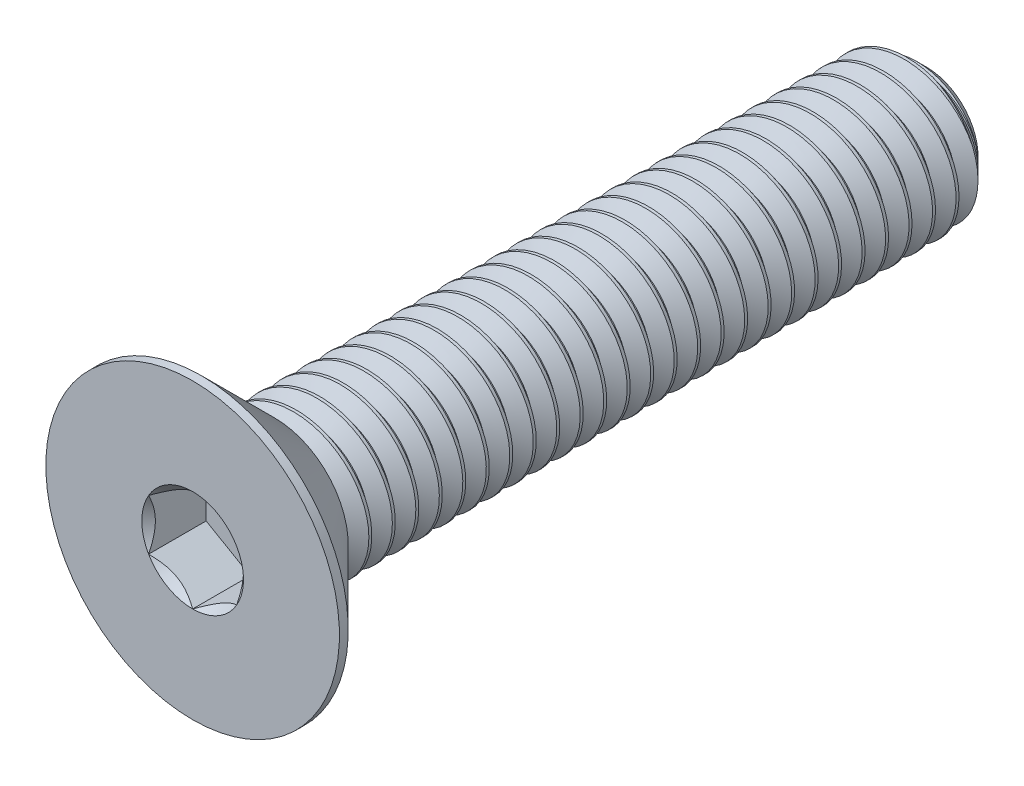
SolidWorks part; units mm, degrees
ref_plane "Front" through (0, 0, 0) normal (0, 0, 1) x (1, 0, 0)
ref_plane "Top" through (0, 0, 0) normal (0, 1, 0) x (1, 0, 0)
ref_plane "Right" through (0, 0, 0) normal (1, 0, 0) x (0, 0, -1)
sketch "Sketch1" plane through (0, 0, 0) normal (1, 0, 0) x (0, 0, -1)
  line L0 (-12.5, 5) -> (-12.2, 5) construction
  line L1 (-12.2, 5) -> (-9.7, 2.5) construction
  line L2 (-12.5, 2.5) -> (12.5, 2.5) construction
  line L3 (12.5, 2.5) -> (12.5, 0) construction
  line L4 (12.5, 0) -> (-12.5, 0) construction
  line L5 (-12.5, 0) -> (-12.5, 5) construction
  line L6 (-12.5, 5) -> (-12.5, -5) construction
  line L7 (12.5, 2.5) -> (12.5, -2.5) construction
  line L8 (-12.5, -5) -> (-12.2, -5) construction
  line L9 (-12.2, -5) -> (-9.7, -2.5) construction
  line L11 (-12.5, 2.5) -> (-12.5, 0) construction
  line L12 (-9.7, 2.5) -> (-9.7, 0) construction
  line L13 (12.45, 2.5866) -> (12.85, 1.8938) construction
  line L14 (12.85, 1.8938) -> (13.25, 2.5866) construction
  line L15 (13.25, 2.5866) -> (12.45, 2.5866) construction
  line L16 (12.85, 2.5866) -> (12.85, 2.5) construction
  line L17 (12.85, 2.5) -> (12.85, 1.9804) construction
  line L18 (12.85, 1.9804) -> (12.85, 1.8938) construction
  line L19 (12.85, 2.5433) -> (13.225, 2.5433) construction
  line L20 (12.85, 2.5433) -> (12.475, 2.5433) construction
  line L21 (12.5, 2.5) -> (13.2, 2.5) construction
  line L22 (12.8, 1.9804) -> (12.9, 1.9804) construction
  line L23 (12.5, -2.5) -> (-9.7, -2.5) construction
  point P10 (10.5, -2.5)
  point P24 (-9.7, 2.5)
  point P30 (0, 0)
  dimension "Head Diameter" = 10
  dimension "Head Height" = 2.8
  dimension "Length" = 25
  dimension "Countersink Angle" = 90
  dimension "Thread Pitch" = 0.8
  dimension "D2" = 0.1
  dimension "Minimum Thread Length" = 22.2
  dimension "Thread Size" = 5
  dimension "D1" = 2
sketch "Sketch2" plane through (0, 0, 0) normal (0, 0, 1) x (1, 0, 0)
  line L1 (0, 1.7321) -> (-1.5, 0.866) construction
  line L2 (-1.5, 0.866) -> (-1.5, -0.866) construction
  line L3 (-1.5, -0.866) -> (0, -1.7321) construction
  line L4 (0, -1.7321) -> (1.5, -0.866) construction
  line L5 (1.5, -0.866) -> (1.5, 0.866) construction
  line L6 (1.5, 0.866) -> (0, 1.7321) construction
  circle A0 centre (0, 0) radius 1.5 construction
  dimension "Drive Size" = 3
sketch "Sketch3" plane through (0, 0, 0) normal (1, 0, 0) x (0, 0, -1)
  line L0 (-12.5, 2.5) -> (12.5, 2.5)
  line L1 (12.5, 2.5) -> (12.5, 0)
  line L2 (12.5, 0) -> (-12.5, 0)
  line L3 (-12.5, 0) -> (-12.5, 2.5)
revolve "Revolve1" add sketch "Sketch3" angle 360 about L4
chamfer "Chamfer1" distance 0.75 angle 45 1 edges at (0, 2.5, -12.5)
sketch "Sketch6" plane through (0, 0, 0) normal (1, 0, 0) x (0, 0, -1)
  line L0 (-12.5, 5) -> (-12.2, 5)
  line L1 (-12.2, 5) -> (-9.7, 2.5)
  line L2 (-9.7, 2.5) -> (-9.7, 0)
  line L3 (-9.7, 0) -> (-12.5, 0)
  line L4 (-12.5, 0) -> (-12.5, 5)
revolve "Revolve2" add sketch "Sketch6" angle 360 about L4
sketch "Sketch8" plane through (0, 0, 12.5) normal (0, 0, 1) x (1, 0, 0)
  line L0 (0, 1.7321) -> (-1.5, 0.866) construction
  line L1 (1.5, 0.866) -> (0, 1.7321) construction
  line L2 (1.5, -0.866) -> (1.5, 0.866) construction
  line L3 (0, -1.7321) -> (1.5, -0.866) construction
  line L4 (-1.5, 0.866) -> (-1.5, -0.866) construction
  line L5 (-1.5, -0.866) -> (0, -1.7321) construction
  line L6 (0, 1.7321) -> (-1.5, 0.866)
  line L7 (1.5, 0.866) -> (0, 1.7321)
  line L8 (1.5, -0.866) -> (1.5, 0.866)
  line L9 (0, -1.7321) -> (1.5, -0.866)
  line L10 (-1.5, 0.866) -> (-1.5, -0.866)
  line L11 (-1.5, -0.866) -> (0, -1.7321)
extrude "Cut-Extrude1" cut sketch "Sketch8" against normal blind 1.96
sketch "Sketch9" plane through (0, 0, 12.5) normal (0, 0, 1) x (1, 0, 0)
  circle A0 centre (0, 0) radius 1.7321
extrude "Cut-Extrude2" cut sketch "Sketch9" against normal up to next (1.96 mm away) draft 45
ref_plane "Plane1" through (0, 0, 9.7) normal (0, 0, 1) x (1, 0, 0)
split "Split1" trim tools "Plane1" bodies to split 124 resulting bodies 126 127
sketch "Sketch4" plane through (0, 0, -12.5) normal (0, 0, -1) x (-1, 0, 0)
  circle A0 centre (0, 0) radius 2.5 construction
  circle A1 centre (0, 0) radius 2.5
curve "Helix/Spiral1" pitch 0.8 height 23 turns 28.75
sketch "Sketch10" plane through (0, 0, 0) normal (1, 0, 0) x (0, 0, -1)
  line L0 (12.475, 2.5433) -> (13.225, 2.5433)
  line L1 (13.225, 2.5433) -> (12.9, 1.9804)
  line L2 (12.9, 1.9804) -> (12.8, 1.9804)
  line L3 (12.8, 1.9804) -> (12.475, 2.5433)
sweep "Cut-Sweep1" cut profiles "Sketch10" path "Helix/Spiral1"
equation "\"D2@Sketch1\" = \"Thread Pitch@Sketch1\" / 8"
equation "\"D4@Helix/Spiral1\"=\"Thread Pitch@Sketch1\""
equation "\"D3@Helix/Spiral1\"=\"Minimum Thread Length@Sketch1\"+\"Thread Pitch@Sketch1\""
equation "\"D1@Chamfer1\"=\"Thread Size@Sketch1\"*.15"
equation "\"D1@Cut-Extrude1\"=\"Head Height@Sketch1\"*.7"
equation "\"D1@Sketch1\"=\"Thread Pitch@Sketch1\"*2.5"
